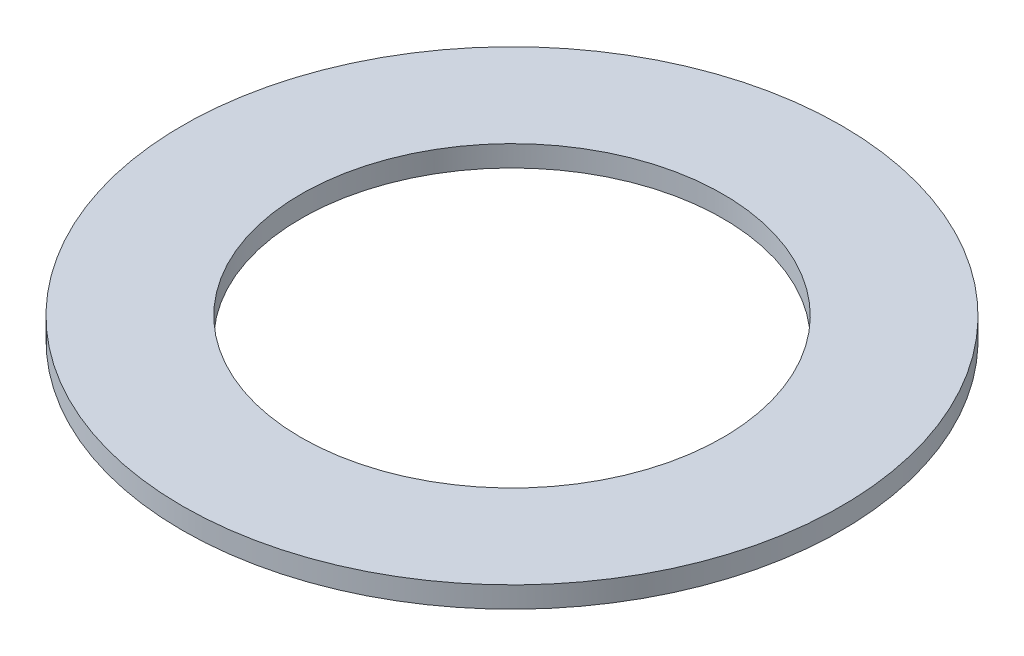
SolidWorks part; units mm, degrees
ref_plane "Front Plane" through (0, 0, 0) normal (0, 0, 1) x (1, 0, 0)
ref_plane "Top Plane" through (0, 0, 0) normal (0, 1, 0) x (1, 0, 0)
ref_plane "Right Plane" through (0, 0, 0) normal (1, 0, 0) x (0, 0, -1)
sketch "Sketch1" plane through (0, 0, 0) normal (0, 1, 0) x (1, 0, 0)
  circle A0 centre (0, 0) radius 62.5
  dimension "FLANGE_OD" = 125
extrude "Boss-Extrude1" add sketch "Sketch1" along normal blind 4
sketch "Sketch2" plane through (0, 0, 0) normal (0, 1, 0) x (1, 0, 0)
  circle A0 centre (0, 0) radius 40
  dimension "BORE_D" = 80
extrude "Cut-Extrude1" cut sketch "Sketch2" along normal through all
sketch "Sketch3" plane through (0, 4, 0) normal (0, 1, 0) x (1, 0, 0)
  circle A0 centre (0, 0) radius 28.1126 construction
  circle A1 centre (-28.1126, 0) radius 3.836
  dimension "BOLT_D" = 7.6721
  dimension "BOLT_PCD" = 56.2253
extrude "Cut-Extrude2" cut sketch "Sketch3" against normal blind 2.6001 rebuild error yes
pattern_circular "CirPattern1" count 8 over 360 rebuild error yes
